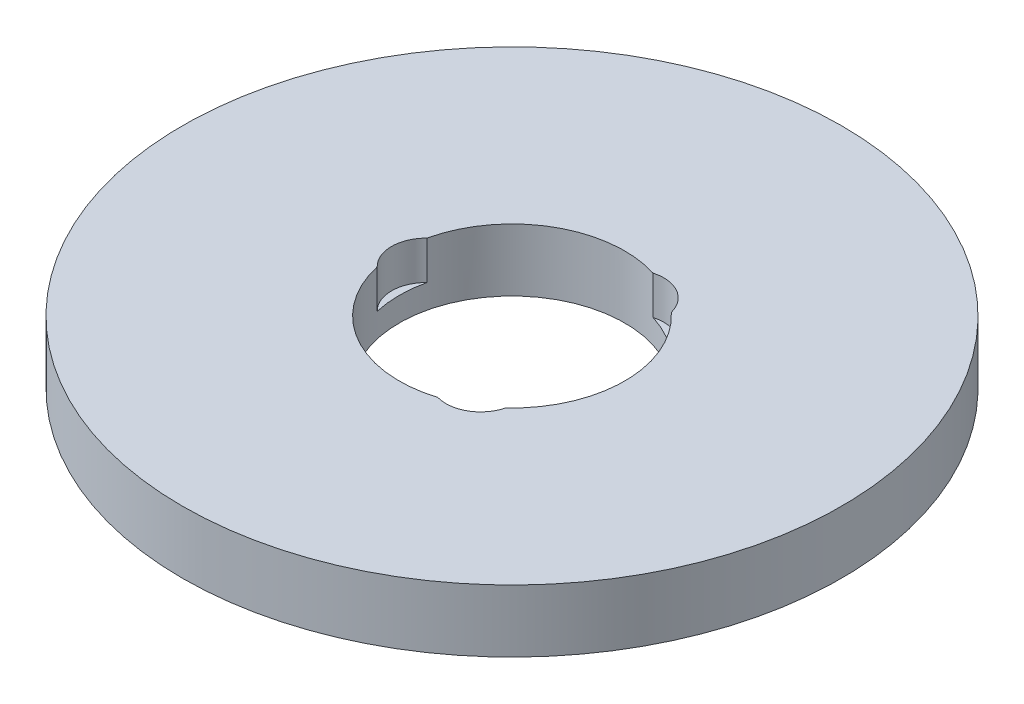
SolidWorks part; units mm, degrees
ref_plane "Front Plane" through (0, 0, 0) normal (0, 0, 1) x (1, 0, 0)
ref_plane "Top Plane" through (0, 0, 0) normal (0, 1, 0) x (1, 0, 0)
ref_plane "Right Plane" through (0, 0, 0) normal (1, 0, 0) x (0, 0, -1)
sketch "Sketch1" plane through (0, 0, 0) normal (0, 1, 0) x (1, 0, 0)
  circle A0 centre (0, 0) radius 95
  dimension "FLANGE_OD" = 190
extrude "Boss-Extrude1" add sketch "Sketch1" along normal blind 18
sketch "Sketch2" plane through (0, 0, 0) normal (0, 1, 0) x (1, 0, 0)
  circle A0 centre (0, 0) radius 32.5
  dimension "BORE_D" = 65
extrude "Cut-Extrude1" cut sketch "Sketch2" along normal through all
sketch "Sketch3" plane through (0, 18, 0) normal (0, 1, 0) x (1, 0, 0)
  circle A0 centre (0, 0) radius 24.7259 construction
  circle A1 centre (-24.7259, 0) radius 10
  dimension "BOLT_D" = 20
  dimension "BOLT_PCD" = 49.4519
extrude "Cut-Extrude2" cut sketch "Sketch3" against normal blind 11.0949
pattern_circular "CirPattern1" count 3 over 360 about axis through (0, 0, 0) along (0, 1, 0) of "Cut-Extrude2"
